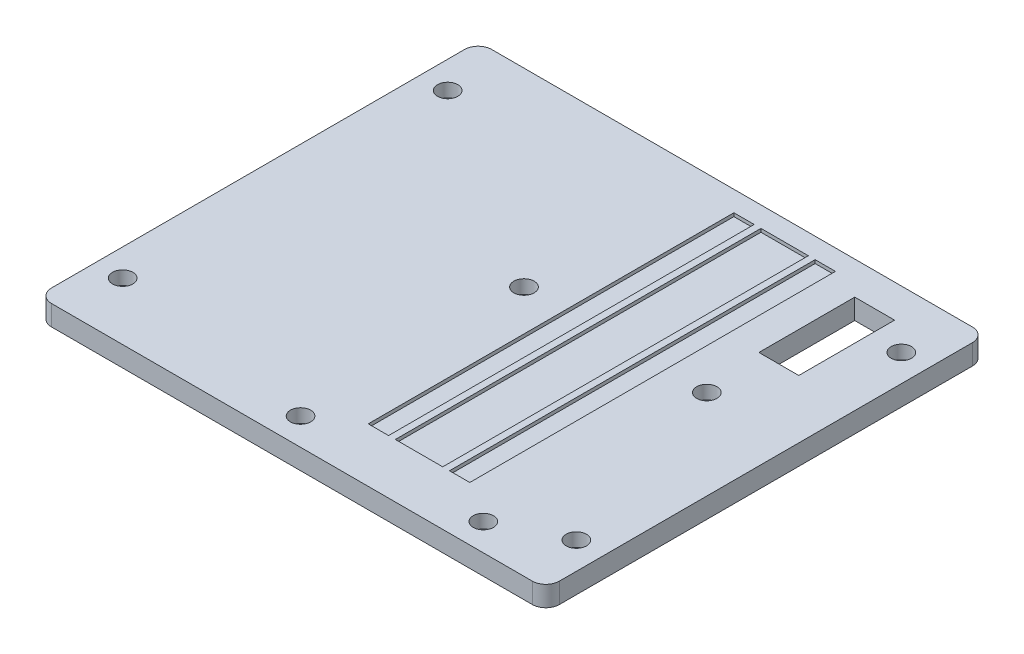
SolidWorks part; units mm, degrees
ref_plane "Alzado" through (0, 0, 0) normal (0, 0, 1) x (1, 0, 0)
ref_plane "Planta" through (0, 0, 0) normal (0, 1, 0) x (1, 0, 0)
ref_plane "Vista lateral" through (0, 0, 0) normal (1, 0, 0) x (0, 0, -1)
sketch "Croquis9" plane through (0, 0, 0) normal (0, 0, 1) x (1, 0, 0)
  line L0 (0, 17.7123) -> (0, -23.4478) construction
  line L1 (0, 10.708) -> (-22, 10.708)
  line L2 (-22, 10.708) -> (-22, 7.708)
  line L3 (-22, 7.708) -> (-13.4884, 7.708)
  line L4 (-13.4884, 7.708) -> (-4.5, 6.708)
  line L5 (-4.5, 6.708) -> (-4.5, -1.292)
  line L6 (-4.5, -1.292) -> (0, -1.292)
  line L7 (0, 10.708) -> (0, -1.292)
  dimension "D1" = 22
  dimension "D2" = 4.5
  dimension "D3" = 3
  dimension "D4" = 1
  dimension "D5" = 8
revolve "Revolución3" add sketch "Croquis9" angle 360 about L0
sketch "Croquis17" plane through (0, 0, 0) normal (1, 0, 0) x (0, 0, -1)
  line L0 (-4.5, -1.292) -> (4.5, -1.292) construction
  circle A0 centre (0, 4.708) radius 1.5
  dimension "D1" = 3
  dimension "D2" = 6
extrude "Cortar-Extruir7" cut sketch "Croquis17" along normal up to next
sketch "Croquis18" plane through (0, 10.708, 0) normal (0, 1, 0) x (1, 0, 0)
  line L0 (1, 2.9343) -> (1, -2.9343)
  arc A0 (1, 2.9343) -> (1, -2.9343) centre (0, 0) ccw
  dimension "D1" = 6.2
  dimension "D2" = 1
extrude "Cortar-Extruir10" cut sketch "Croquis18" against normal blind 6 from offset 3 offset against normal yes
sketch "Croquis21" plane through (0, 0, 0) normal (0, 0, 1) x (1, 0, 0)
  line L0 (0, 3.5811) -> (0, -1.3759) construction
  line L1 (0, 1.8085) -> (-3.1, 1.8085)
  line L2 (-3.1, 1.8085) -> (-3.1, -1.6716)
  line L3 (-3.1, -1.6716) -> (0, -1.6716)
  line L4 (0, 1.8085) -> (0, -1.6716)
  dimension "D1" = 3.1
revolve "Cortar-Revolución1" cut sketch "Croquis21" angle 360 about L0
chamfer "Chaflán2" distance 0.5 angle 45 1 edges at (1, 1.8085, 0)
chamfer "Chaflán1" [suppressed] distance 0.5 angle 45
sketch "Croquis22" plane through (0, 10.708, 0) normal (0, 1, 0) x (1, 0, 0)
  line L1 (-37.5, -32.5) -> (37.5, -32.5)
  line L2 (-37.5, -32.5) -> (-37.5, 32.5)
  line L3 (-37.5, 32.5) -> (37.5, 32.5)
  line L4 (37.5, -32.5) -> (37.5, 32.5)
  line L5 (-37.5, -32.5) -> (37.5, 32.5) construction
  line L6 (-37.5, 32.5) -> (37.5, -32.5) construction
  point P0 (0, 0)
  dimension "D1" = 65
  dimension "D2" = 75
extrude "Saliente-Extruir1" add sketch "Croquis22" against normal up to surface (3 mm away) up to face at (0, 7.708, 13.4884)
fillet "Redondeo1" radius 2 4 edges at (-37.5, 9.208, -32.5) (37.5, 9.208, -32.5) (37.5, 9.208, 32.5) (-37.5, 9.208, 32.5)
sketch "Croquis23" plane through (0, 10.708, 0) normal (0, 1, 0) x (1, 0, 0)
  circle A0 centre (-33.5, 24) radius 1.5
  circle A1 centre (-33.5, -24) radius 1.5
  circle A2 centre (33.5, -24) radius 1.5
  circle A3 centre (33.5, 24) radius 1.5
  dimension "D1" = 3
  dimension "D4" = 48
  dimension "D3" = 33.5
  dimension "D2" = 67
  dimension "D5" = 24
extrude "Cortar-Extruir11" cut sketch "Croquis23" against normal blind 2
sketch "Croquis24" plane through (0, 10.708, 0) normal (0, 1, 0) x (1, 0, 0)
  line L0 (-35.5, -32.5) -> (35.5, -32.5) construction
  line L1 (3.27, 29.5) -> (18.27, 29.5)
  line L2 (3.27, 29.5) -> (3.27, -24.5)
  line L3 (3.27, -24.5) -> (18.27, -24.5)
  line L4 (18.27, 29.5) -> (18.27, -24.5)
  line L5 (6.27, 29.5) -> (7.27, 29.5)
  line L6 (6.27, 29.5) -> (6.27, -24.5)
  line L7 (6.27, -24.5) -> (7.27, -24.5)
  line L8 (7.27, 29.5) -> (7.27, -24.5)
  line L9 (14.27, 29.5) -> (15.27, 29.5)
  line L10 (14.27, 29.5) -> (14.27, -24.5)
  line L11 (14.27, -24.5) -> (15.27, -24.5)
  line L12 (15.27, 29.5) -> (15.27, -24.5)
  line L13 (35.5, 32.5) -> (-35.5, 32.5) construction
  dimension "D1" = 3
  dimension "D2" = 15
  dimension "D3" = 1
  dimension "D4" = 1
  dimension "D5" = 3.27
  dimension "D6" = 3
  dimension "D7" = 3
  dimension "D8" = 8
extrude "Cortar-Extruir12" cut sketch "Croquis24" against normal blind 0.5 contours L6 L1 L2 L3 | L10 L1 L8 L3 | L1 L12 L3 L4 region at (4.77, 10.708, -2.5) region at (10.77, 10.708, -2.5) region at (16.77, 10.708, -2.5)
sketch "Croquis25" plane through (0, 10.708, 0) normal (0, 1, 0) x (1, 0, 0)
  line L0 (3.27, 29.5) -> (3.27, -24.5) construction
  line L1 (18.27, 29.5) -> (18.27, -24.5) construction
  line L3 (-35.5, -32.5) -> (35.5, -32.5) construction
  circle A0 centre (-2.73, -28.5) radius 1.5
  circle A1 centre (24.27, -28.5) radius 1.5
  circle A2 centre (33.5, -24) radius 1.5 construction
  circle A3 centre (33.5, -24) radius 1.5 construction
  circle A6 centre (-2.73, 4.5) radius 1.5
  circle A7 centre (24.27, 4.5) radius 1.5
  dimension "D2" = 6
  dimension "D1" = 6
  dimension "D4" = 4
  dimension "D5" = 33
  dimension "D3" = 2
extrude "Cortar-Extruir13" cut sketch "Croquis25" against normal blind 2
sketch "Croquis26" plane through (0, 10.708, 0) normal (0, 1, 0) x (1, 0, 0)
  line L1 (22.988, 27.6308) -> (28.8765, 27.6308)
  line L2 (22.988, 27.6308) -> (22.988, 13.4757)
  line L3 (22.988, 13.4757) -> (28.8765, 13.4757)
  line L4 (28.8765, 27.6308) -> (28.8765, 13.4757)
extrude "Cortar-Extruir14" cut sketch "Croquis26" against normal blind 10
